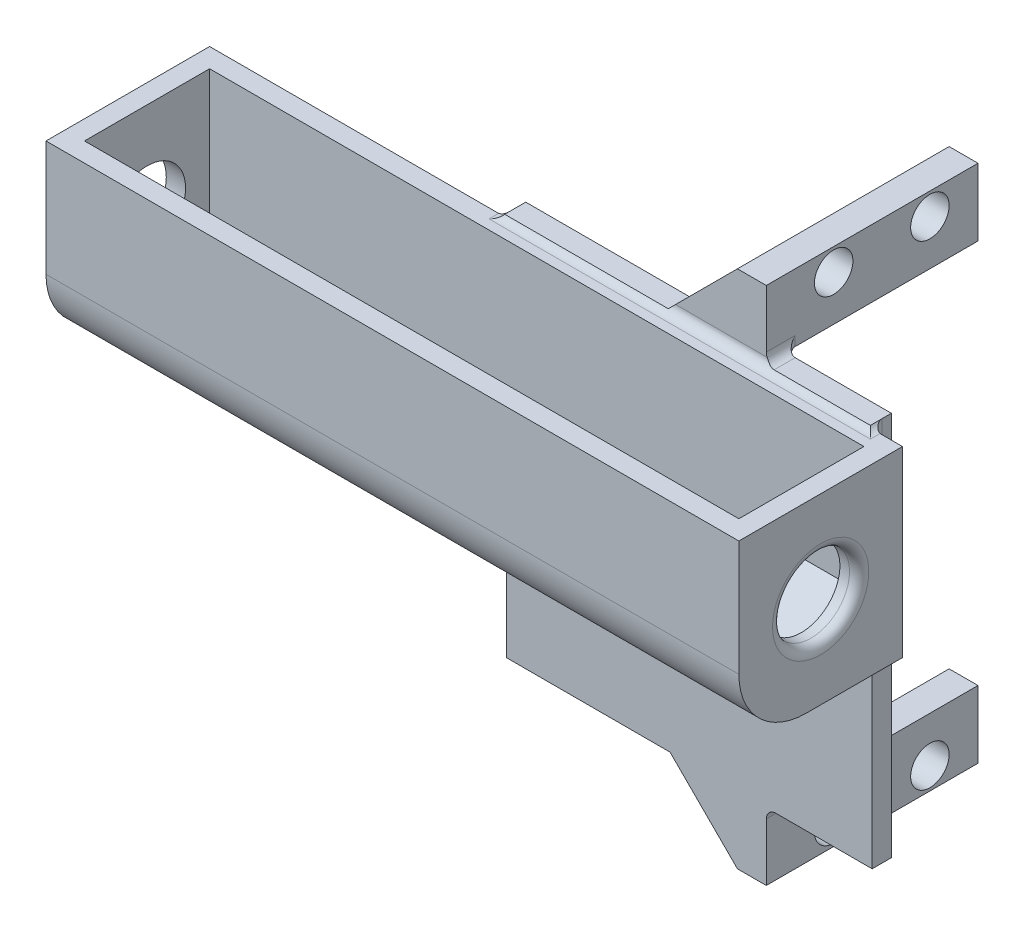
SolidWorks part; units mm, degrees
material "ABS"
ref_plane "Front Plane" through (0, 0, 0) normal (0, 0, 1) x (1, 0, 0)
ref_plane "Top Plane" through (0, 0, 0) normal (0, 1, 0) x (1, 0, 0)
ref_plane "Right Plane" through (0, 0, 0) normal (1, 0, 0) x (0, 0, -1)
sketch "Sketch1" plane through (0, 0, 0) normal (0, 0, 1) x (1, 0, 0)
  line L1 (0, 0) -> (38, 0)
  line L2 (0, 0) -> (0, 54)
  line L3 (0, 54) -> (38, 54)
  line L4 (38, 0) -> (38, 54)
  dimension "D1" = 38
  dimension "D2" = 54
extrude "Boss-Extrude2" add sketch "Sketch1" along normal blind 2
sketch "Sketch2" plane through (0, 0, 2) normal (0, 0, 1) x (1, 0, 0)
  line L0 (0, 47) -> (24, 47)
  line L1 (0, 54) -> (0, 0) construction
  line L2 (24, 47) -> (24, 54)
  line L3 (38, 54) -> (0, 54) construction
  line L4 (24, 54) -> (0, 54)
  line L5 (0, 54) -> (0, 47)
  line L6 (0, 7) -> (24, 7)
  line L7 (24, 7) -> (24, 0)
  line L8 (0, 0) -> (38, 0) construction
  line L9 (24, 0) -> (0, 0)
  line L10 (0, 0) -> (0, 7)
  line L11 (27, 54) -> (27, 47)
  line L12 (27, 47) -> (38, 47)
  line L13 (38, 0) -> (38, 54) construction
  line L14 (38, 47) -> (38, 54)
  line L15 (38, 54) -> (27, 54)
  line L16 (27, 0) -> (27, 7)
  line L17 (27, 7) -> (38, 7)
  line L18 (27, 0) -> (38, 0)
  line L19 (38, 0) -> (38, 7)
  dimension "D1" = 11
  dimension "D2" = 7
  dimension "D3" = 3
  dimension "D4" = 7
  dimension "D5" = 3
  dimension "D6" = 7
  dimension "D7" = 7
  dimension "D8" = 11
extrude "Cut-Extrude1" cut sketch "Sketch2" against normal blind 2
sketch "Sketch3" plane through (0, 0, 0) normal (0, 0, -1) x (-1, 0, 0)
  line L1 (-27, 47) -> (-24, 47)
  line L2 (-27, 47) -> (-27, 54)
  line L3 (-27, 54) -> (-24, 54)
  line L4 (-24, 47) -> (-24, 54)
  line L5 (-27, 0) -> (-24, 0)
  line L6 (-27, 0) -> (-27, 7)
  line L7 (-27, 7) -> (-24, 7)
  line L8 (-24, 0) -> (-24, 7)
extrude "Boss-Extrude3" add sketch "Sketch3" along normal blind 20
sketch "Sketch4" plane through (0, 0, 2) normal (0, 0, 1) x (1, 0, 0)
  line L0 (24, 7) -> (24, 0)
  line L1 (24, 0) -> (17, 7)
  line L2 (24, 7) -> (0, 7) construction
  line L3 (17, 7) -> (24, 7)
  line L4 (24, 47) -> (17, 47)
  line L5 (0, 47) -> (24, 47) construction
  line L6 (17, 47) -> (24, 54)
  line L7 (24, 54) -> (24, 47)
extrude "Boss-Extrude4" add sketch "Sketch4" against normal blind 2
sketch "Sketch5" plane through (27, 0, 0) normal (1, 0, 0) x (0, 0, -1)
  line L0 (20, 7) -> (20, 0) construction
  line L1 (-2, 7) -> (-2, 0) construction
  line L2 (20, 7) -> (0, 7) construction
  line L3 (20, 54) -> (20, 47) construction
  line L4 (20, 47) -> (0, 47) construction
  line L5 (-2, 54) -> (-2, 47) construction
  circle A0 centre (15, 2.3) radius 2
  circle A1 centre (5, 2.3) radius 2
  circle A2 centre (15, 51.7) radius 2
  circle A3 centre (5, 51.7) radius 2
  dimension "D1" = 4
  dimension "D2" = 5
  dimension "D6" = 4
  dimension "D3" = 7
  dimension "D4" = 4.7
  dimension "D5" = 4.7
  dimension "D7" = 5
  dimension "D8" = 4.7
  dimension "D9" = 7
  dimension "D10" = 4.7
extrude "Cut-Extrude3" cut sketch "Sketch5" against normal through all
sketch "Sketch7" plane through (0, 0, 2) normal (0, 0, 1) x (1, 0, 0)
  line L0 (27, 47) -> (38, 47) construction
  line L1 (-30.85, 46.58) -> (41.15, 46.58)
  line L2 (-30.85, 46.58) -> (-30.85, 27.58)
  line L3 (-30.85, 27.58) -> (41.15, 27.58)
  line L4 (41.15, 46.58) -> (41.15, 27.58)
  line L5 (38, 7) -> (38, 47) construction
  dimension "D1" = 0.42
  dimension "D2" = 19
  dimension "D3" = 3.15
  dimension "D4" = 72
extrude "Boss-Extrude5" add sketch "Sketch7" along normal blind 17
sketch "Sketch6" plane through (27, 0, 0) normal (1, 0, 0) x (0, 0, -1)
  line L0 (0, 7) -> (0, 47) construction
  line L1 (20, 7) -> (0, 7) construction
  line L7 (-2, 46.58) -> (-2, 27.58) construction
  line L10 (-4, 40.8386) -> (-10.5, 44.5914) construction
  line L11 (-10.5, 44.5914) -> (-17, 40.8386) construction
  line L12 (-17, 40.8386) -> (-17, 33.333) construction
  line L13 (-17, 33.333) -> (-10.5, 29.5803) construction
  line L14 (-10.5, 29.5803) -> (-4, 33.333) construction
  line L15 (-4, 33.333) -> (-4, 40.8386) construction
  circle A0 centre (10, 17) radius 3 construction
  circle A1 centre (10, 17) radius 28.7 construction
  circle A2 centre (-10.5, 37.0858) radius 15 construction
  circle A3 centre (10, 17) radius 15 construction
  circle A5 centre (-10.5, 37.0858) radius 4
  circle A6 centre (-10.5, 37.0858) radius 6.5 construction
  dimension "D3" = 6
  dimension "D4" = 57.4
  dimension "D5" = 30
  dimension "D6" = 30
  dimension "D7" = 2
  dimension "D8" = 13
  dimension "D1" = 10
  dimension "D2" = 10
extrude "Cut-Extrude4" cut sketch "Sketch6" against normal through all both and the other way through all
sketch "Sketch8" plane through (-30.85, 0, 0) normal (-1, 0, 0) x (0, 0, 1)
  line L1 (10.5, 44.5914) -> (4, 40.8386)
  line L2 (4, 40.8386) -> (4, 33.333)
  line L3 (4, 33.333) -> (10.5, 29.5803)
  line L4 (10.5, 29.5803) -> (17, 33.333)
  line L5 (17, 33.333) -> (17, 40.8386)
  line L6 (17, 40.8386) -> (10.5, 44.5914)
  circle A0 centre (10.5, 37.0858) radius 6.5 construction
  dimension "D1" = 13
extrude "Cut-Extrude5" cut sketch "Sketch8" against normal blind 68 from offset 2 offset against normal yes
sketch "Sketch9" plane through (0, 46.58, 0) normal (0, 1, 0) x (1, 0, 0)
  line L0 (41.15, -19) -> (-30.85, -19) construction
  line L1 (-28.85, -17) -> (39.15, -17)
  line L2 (-28.85, -17) -> (-28.85, -4)
  line L3 (-28.85, -4) -> (39.15, -4)
  line L4 (39.15, -17) -> (39.15, -4)
  line L5 (41.15, -19) -> (41.15, -2) construction
  line L6 (-30.85, -19) -> (-30.85, -2) construction
  dimension "D1" = 13
  dimension "D2" = 2
  dimension "D3" = 2
  dimension "D4" = 2
extrude "Cut-Extrude6" cut sketch "Sketch9" against normal blind 7
fillet "Fillet1" radius 1 1 edges at (41.15, 37.0858, 6.5)
fillet "Fillet2" radius 1 1 edges at (19, 27.58, 2)
fillet "Fillet3" radius 1 1 edges at (38, 37.08, 2)
fillet "Fillet4" radius 1 1 edges at (38, 27.58, 2)
fillet "Fillet5" radius 1 2 edges at (19, 46.58, 2) (38, 46.58, 1.5)
fillet "Fillet6" radius 1 2 edges at (25.5, 47, 0) (24, 50.5, 0)
fillet "Fillet7" radius 1 2 edges at (0, 37.08, 2) (0, 46.58, 2.5)
fillet "Fillet8" radius 1 1 edges at (0, 27.58, 2)
fillet "Fillet9" radius 1 2 edges at (27, 46.5, 0) (27, 47, 1.0927)
fillet "Fillet10" radius 1 1 edges at (27, 7, 1)
fillet "Fillet11" radius 1 3 edges at (24, 3.5, 0) (25.5, 7, 0) (27, 6.5, 0)
fillet "Fillet12" radius 7 1 edges at (5.15, 27.58, 19)
